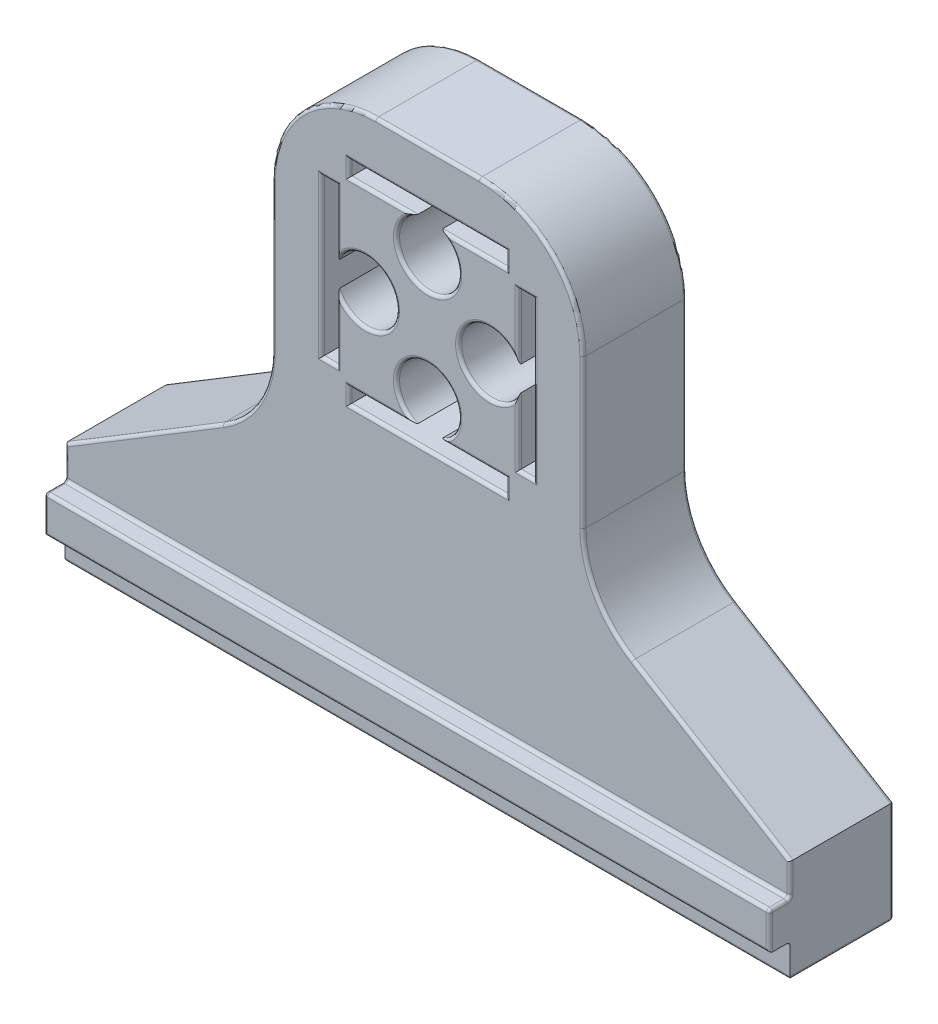
SolidWorks part; units mm, degrees
ref_plane "Front Plane" through (0, 0, 0) normal (0, 0, 1) x (1, 0, 0)
ref_plane "Top Plane" through (0, 0, 0) normal (0, 1, 0) x (1, 0, 0)
ref_plane "Right Plane" through (0, 0, 0) normal (1, 0, 0) x (0, 0, -1)
sketch "Sketch1" plane through (0, 0, 0) normal (0, 0, 1) x (1, 0, 0)
  line L0 (-8.65, 7.69) -> (-8.65, 1.6086)
  line L1 (-8.65, 7.69) -> (-10.35, 7.69)
  line L2 (-10.35, 7.69) -> (-10.35, -7.69)
  line L3 (-10.35, -7.69) -> (-8.65, -7.69)
  line L4 (-6, 0) -> (-10.35, 0) construction
  line L5 (-8.65, -1.6086) -> (-8.65, -7.69)
  line L6 (-8.65, 7.69) -> (-8.65, -7.69) construction
  line L7 (7.69, 8.65) -> (1.6086, 8.65)
  line L8 (7.69, 8.65) -> (7.69, 10.35)
  line L9 (7.69, 10.35) -> (-7.69, 10.35)
  line L10 (-7.69, 10.35) -> (-7.69, 8.65)
  line L11 (8.65, -7.69) -> (8.65, -1.6086)
  line L12 (8.65, -7.69) -> (10.35, -7.69)
  line L13 (10.35, -7.69) -> (10.35, 7.69)
  line L14 (10.35, 7.69) -> (8.65, 7.69)
  line L15 (-7.69, -8.65) -> (-1.6086, -8.65)
  line L16 (-7.69, -8.65) -> (-7.69, -10.35)
  line L17 (-7.69, -10.35) -> (7.69, -10.35)
  line L18 (7.69, -10.35) -> (7.69, -8.65)
  line L19 (1.6086, -8.65) -> (7.69, -8.65)
  line L20 (8.65, 1.6086) -> (8.65, 7.69)
  line L21 (-1.6086, 8.65) -> (-7.69, 8.65)
  circle A0 centre (0, 0) radius 6 construction
  circle A1 centre (0, 6) radius 2
  circle A2 centre (6, 0) radius 2
  circle A3 centre (0, -6) radius 2
  circle A4 centre (-6, 0) radius 2
  arc A5 (-1.6086, 8.65) -> (1.6086, 8.65) centre (0, 6) ccw
  arc A6 (-8.65, -1.6086) -> (-8.65, 1.6086) centre (-6, 0) ccw
  arc A7 (1.6086, -8.65) -> (-1.6086, -8.65) centre (0, -6) ccw
  arc A8 (8.65, 1.6086) -> (8.65, -1.6086) centre (6, 0) ccw
  circle A9 centre (0, 0) radius 2.9 construction
  circle A10 centre (-6, 0) radius 3.1 construction
  circle A11 centre (0, -6) radius 3.1 construction
  circle A12 centre (6, 0) radius 3.1 construction
  circle A13 centre (0, 6) radius 3.1 construction
  point P14 (0, 0)
  point P22 (-10.35, 0)
  point P25 (-5.6596, 0)
  point P43 (0, 0)
  dimension "D1" = 4
  dimension "D4" = 12
  dimension "D5" = 4.35
  dimension "D6" = 1.7
  dimension "D7" = 15.38
  dimension "D3" = 1.1
  dimension "D2" = 4
  dimension "D8" = 4
sketch "Sketch2" plane through (0, 0, 0) normal (0, 0, 1) x (1, 0, 0)
  line L0 (0, 0) -> (0, -37.05) construction
  line L1 (-15, -15) -> (15, -15) construction
  line L2 (-15, -15) -> (-15, 15) construction
  line L3 (-15, 15) -> (15, 15) construction
  line L4 (15, -15) -> (15, 15) construction
  line L5 (-15, -15) -> (15, 15) construction
  line L6 (-15, 15) -> (15, -15) construction
  line L7 (35, -37.05) -> (-35, -37.05) construction
  line L8 (-35, -37.05) -> (-35, -27.15) construction
  line L9 (-35, -27.15) -> (35, -27.15) construction
  line L10 (35, -27.15) -> (35, -37.05) construction
  line L11 (-15, -15) -> (-35, -27.15) construction
  line L12 (15, -15) -> (35, -27.15) construction
  point P0 (0, 0)
  point P11 (0, -37.05)
  dimension "D1" = 30
  dimension "D2" = 37.05
  dimension "D3" = 70
  dimension "D4" = 9.9
sketch "Sketch3" plane through (0, 0, 0) normal (0, 0, 1) x (1, 0, 0)
  line L0 (-7.69, -10.35) -> (7.69, -10.35) construction
  line L1 (7.69, -10.35) -> (7.69, -8.65) construction
  line L2 (1.6086, -8.65) -> (7.69, -8.65) construction
  line L3 (-7.69, -8.65) -> (-1.6086, -8.65) construction
  line L4 (-7.69, -8.65) -> (-7.69, -10.35) construction
  line L5 (10.35, -7.69) -> (10.35, 7.69) construction
  line L6 (10.35, 7.69) -> (8.65, 7.69) construction
  line L7 (8.65, 1.6086) -> (8.65, 7.69) construction
  line L8 (8.65, -7.69) -> (8.65, -1.6086) construction
  line L9 (8.65, -7.69) -> (10.35, -7.69) construction
  line L10 (-1.6086, 8.65) -> (-7.69, 8.65) construction
  line L11 (-7.69, 10.35) -> (-7.69, 8.65) construction
  line L12 (7.69, 10.35) -> (-7.69, 10.35) construction
  line L13 (7.69, 8.65) -> (7.69, 10.35) construction
  line L14 (7.69, 8.65) -> (1.6086, 8.65) construction
  line L15 (-10.35, 7.69) -> (-10.35, -7.69) construction
  line L16 (-10.35, -7.69) -> (-8.65, -7.69) construction
  line L17 (-8.65, -1.6086) -> (-8.65, -7.69) construction
  line L18 (-8.65, 7.69) -> (-8.65, 1.6086) construction
  line L19 (-8.65, 7.69) -> (-10.35, 7.69) construction
  line L20 (-15, -15) -> (-15, 15) construction
  line L21 (-15, 15) -> (15, 15) construction
  line L22 (15, -15) -> (15, 15) construction
  line L23 (15, -15) -> (35, -27.15) construction
  line L24 (-15, -15) -> (-35, -27.15) construction
  line L25 (35, -37.05) -> (-35, -37.05) construction
  line L26 (35, -27.15) -> (35, -37.05) construction
  line L27 (-35, -37.05) -> (-35, -27.15) construction
  line L28 (-7.69, -10.35) -> (7.69, -10.35)
  line L29 (7.69, -10.35) -> (7.69, -8.65)
  line L30 (1.6086, -8.65) -> (7.69, -8.65)
  line L31 (-7.69, -8.65) -> (-1.6086, -8.65)
  line L32 (-7.69, -8.65) -> (-7.69, -10.35)
  line L33 (10.35, -7.69) -> (10.35, 7.69)
  line L34 (10.35, 7.69) -> (8.65, 7.69)
  line L35 (8.65, 1.6086) -> (8.65, 7.69)
  line L36 (8.65, -7.69) -> (8.65, -1.6086)
  line L37 (8.65, -7.69) -> (10.35, -7.69)
  line L38 (-1.6086, 8.65) -> (-7.69, 8.65)
  line L39 (-7.69, 10.35) -> (-7.69, 8.65)
  line L40 (7.69, 10.35) -> (-7.69, 10.35)
  line L41 (7.69, 8.65) -> (7.69, 10.35)
  line L42 (7.69, 8.65) -> (1.6086, 8.65)
  line L43 (-10.35, 7.69) -> (-10.35, -7.69)
  line L44 (-10.35, -7.69) -> (-8.65, -7.69)
  line L45 (-8.65, -1.6086) -> (-8.65, -7.69)
  line L46 (-8.65, 7.69) -> (-8.65, 1.6086)
  line L47 (-8.65, 7.69) -> (-10.35, 7.69)
  line L48 (-15, -15) -> (-15, 15)
  line L49 (-15, 15) -> (15, 15)
  line L50 (15, -15) -> (15, 15)
  line L51 (15, -15) -> (35, -27.15)
  line L52 (-15, -15) -> (-35, -27.15)
  line L53 (35, -37.05) -> (-35, -37.05)
  line L54 (35, -27.15) -> (35, -37.05)
  line L55 (-35, -37.05) -> (-35, -27.15)
  arc A0 (1.6086, -8.65) -> (-1.6086, -8.65) centre (0, -6) ccw construction
  arc A1 (8.65, 1.6086) -> (8.65, -1.6086) centre (6, 0) ccw construction
  arc A2 (-1.6086, 8.65) -> (1.6086, 8.65) centre (0, 6) ccw construction
  arc A3 (-8.65, -1.6086) -> (-8.65, 1.6086) centre (-6, 0) ccw construction
  arc A4 (1.6086, -8.65) -> (-1.6086, -8.65) centre (0, -6) ccw
  arc A5 (8.65, 1.6086) -> (8.65, -1.6086) centre (6, 0) ccw
  arc A6 (-1.6086, 8.65) -> (1.6086, 8.65) centre (0, 6) ccw
  arc A7 (-8.65, -1.6086) -> (-8.65, 1.6086) centre (-6, 0) ccw
  circle A8 centre (0, -6) radius 2 construction
  circle A9 centre (6, 0) radius 2 construction
  circle A10 centre (0, 6) radius 2 construction
  circle A11 centre (-6, 0) radius 2 construction
  circle A12 centre (0, -6) radius 2
  circle A13 centre (6, 0) radius 2
  circle A14 centre (0, 6) radius 2
  circle A15 centre (-6, 0) radius 2
extrude "Boss-Extrude1" add sketch "Sketch3" along normal mid plane 10 contours L55 L53 L54 L51 L50 L49 L48 L52 A7 L45 L44 L43 L47 L46 A6 L38 L39 L40 L41 L42 A5 L35 L34 L33 L37 L36 A4 L30 L29 L28 L32 L31
sketch "Sketch4" plane through (0, 0, -5) normal (0, 0, -1) x (-1, 0, 0)
  line L0 (7.69, -8.65) -> (1.6086, -8.65) construction
  line L1 (7.69, -8.65) -> (7.69, -10.35) construction
  line L2 (7.69, -10.35) -> (-7.69, -10.35) construction
  line L3 (-7.69, -10.35) -> (-7.69, -8.65) construction
  line L4 (-1.6086, -8.65) -> (-7.69, -8.65) construction
  line L5 (8.65, 7.69) -> (8.65, 1.6086) construction
  line L6 (8.65, 7.69) -> (10.35, 7.69) construction
  line L7 (10.35, 7.69) -> (10.35, -7.69) construction
  line L8 (10.35, -7.69) -> (8.65, -7.69) construction
  line L9 (8.65, -1.6086) -> (8.65, -7.69) construction
  line L10 (1.6086, 8.65) -> (7.69, 8.65) construction
  line L11 (7.69, 10.35) -> (7.69, 8.65) construction
  line L12 (-7.69, 10.35) -> (7.69, 10.35) construction
  line L13 (-7.69, 8.65) -> (-7.69, 10.35) construction
  line L14 (-7.69, 8.65) -> (-1.6086, 8.65) construction
  line L15 (-8.65, 1.6086) -> (-8.65, 7.69) construction
  line L16 (-10.35, 7.69) -> (-8.65, 7.69) construction
  line L17 (-10.35, -7.69) -> (-10.35, 7.69) construction
  line L18 (-8.65, -7.69) -> (-10.35, -7.69) construction
  line L19 (-8.65, -7.69) -> (-8.65, -1.6086) construction
  line L20 (7.69, -8.65) -> (1.6086, -8.65)
  line L21 (7.69, -8.65) -> (7.69, -10.35)
  line L22 (7.69, -10.35) -> (-7.69, -10.35)
  line L23 (-7.69, -10.35) -> (-7.69, -8.65)
  line L24 (-1.6086, -8.65) -> (-7.69, -8.65)
  line L25 (8.65, 7.69) -> (8.65, 1.6086)
  line L26 (8.65, 7.69) -> (10.35, 7.69)
  line L27 (10.35, 7.69) -> (10.35, -7.69)
  line L28 (10.35, -7.69) -> (8.65, -7.69)
  line L29 (8.65, -1.6086) -> (8.65, -7.69)
  line L30 (1.6086, 8.65) -> (7.69, 8.65)
  line L31 (7.69, 10.35) -> (7.69, 8.65)
  line L32 (-7.69, 10.35) -> (7.69, 10.35)
  line L33 (-7.69, 8.65) -> (-7.69, 10.35)
  line L34 (-7.69, 8.65) -> (-1.6086, 8.65)
  line L35 (-8.65, 1.6086) -> (-8.65, 7.69)
  line L36 (-10.35, 7.69) -> (-8.65, 7.69)
  line L37 (-10.35, -7.69) -> (-10.35, 7.69)
  line L38 (-8.65, -7.69) -> (-10.35, -7.69)
  line L39 (-8.65, -7.69) -> (-8.65, -1.6086)
  circle A0 centre (6, 0) radius 2 construction
  circle A1 centre (0, 6) radius 2 construction
  circle A2 centre (-6, 0) radius 2 construction
  circle A3 centre (0, -6) radius 2 construction
  arc A4 (1.6086, -8.65) -> (-1.6086, -8.65) centre (0, -6) ccw construction
  arc A5 (8.65, 1.6086) -> (8.65, -1.6086) centre (6, 0) ccw construction
  arc A6 (-1.6086, 8.65) -> (1.6086, 8.65) centre (0, 6) ccw construction
  arc A7 (-8.65, -1.6086) -> (-8.65, 1.6086) centre (-6, 0) ccw construction
  circle A8 centre (6, 0) radius 2
  circle A9 centre (0, 6) radius 2
  circle A10 centre (-6, 0) radius 2
  circle A11 centre (0, -6) radius 2
  arc A12 (1.6086, -8.65) -> (-1.6086, -8.65) centre (0, -6) ccw
  arc A13 (8.65, 1.6086) -> (8.65, -1.6086) centre (6, 0) ccw
  arc A14 (-1.6086, 8.65) -> (1.6086, 8.65) centre (0, 6) ccw
  arc A15 (-8.65, -1.6086) -> (-8.65, 1.6086) centre (-6, 0) ccw
extrude "Boss-Extrude2" add sketch "Sketch4" against normal blind 2
fillet "Fillet1" radius 10 4 edges at (15, -15, 0) (15, 15, 0) (-15, 15, 0) (-15, -15, 0)
sketch "Sketch5" plane through (35, 0, 0) normal (1, 0, 0) x (0, 0, -1)
  line L0 (-7, -33.85) -> (-5, -33.85)
  line L1 (-5, -33.85) -> (-5, -37.05)
  line L2 (-5, -37.05) -> (4.9, -37.05)
  line L3 (4.9, -37.05) -> (4.9, -27.15)
  line L4 (4.9, -27.15) -> (-5, -27.15)
  line L5 (-5, -27.15) -> (-5, -30.25)
  line L6 (-5, -30.25) -> (-7, -30.25)
  line L7 (-7, -30.25) -> (-7, -33.85)
  point P0 (-5, -37.05)
extrude "Boss-Extrude3" add sketch "Sketch5" against normal up to surface (70 mm away) up to face at (-35, -32.1, 0)
fillet "Fillet2" radius 0.3 6 edges at (35, -32.05, 7) (0, -33.85, 7) (-35, -32.05, 7) (0, -30.25, 7) (0, -33.85, 5) (0, -30.25, 5)
sketch "Sketch6" plane through (0, 0, -3) normal (0, 0, 1) x (1, 0, 0)
  line L15 (-8.75, -7.59) -> (-8.75, -1.199)
  line L16 (-10.25, -7.59) -> (-8.75, -7.59)
  line L17 (-10.25, 7.59) -> (-10.25, -7.59)
  line L18 (-8.75, 7.59) -> (-10.25, 7.59)
  line L19 (-8.75, 1.199) -> (-8.75, 7.59)
  line L20 (-8.75, -7.59) -> (-8.75, -1.199)
  line L21 (-10.25, -7.59) -> (-8.75, -7.59)
  line L22 (-10.25, 7.59) -> (-10.25, -7.59)
  line L23 (-8.75, 7.59) -> (-10.25, 7.59)
  line L24 (-8.75, 1.199) -> (-8.75, 7.59)
  line L30 (-7.59, 8.75) -> (-1.199, 8.75)
  line L31 (-7.59, 10.25) -> (-7.59, 8.75)
  line L32 (7.59, 10.25) -> (-7.59, 10.25)
  line L33 (7.59, 8.75) -> (7.59, 10.25)
  line L34 (1.199, 8.75) -> (7.59, 8.75)
  line L35 (-7.59, 8.75) -> (-1.199, 8.75)
  line L36 (-7.59, 10.25) -> (-7.59, 8.75)
  line L37 (7.59, 10.25) -> (-7.59, 10.25)
  line L38 (7.59, 8.75) -> (7.59, 10.25)
  line L39 (1.199, 8.75) -> (7.59, 8.75)
  line L45 (8.75, 7.59) -> (8.75, 1.199)
  line L46 (10.25, 7.59) -> (8.75, 7.59)
  line L47 (10.25, -7.59) -> (10.25, 7.59)
  line L48 (8.75, -7.59) -> (10.25, -7.59)
  line L49 (8.75, -1.199) -> (8.75, -7.59)
  line L50 (8.75, 7.59) -> (8.75, 1.199)
  line L51 (10.25, 7.59) -> (8.75, 7.59)
  line L52 (10.25, -7.59) -> (10.25, 7.59)
  line L53 (8.75, -7.59) -> (10.25, -7.59)
  line L54 (8.75, -1.199) -> (8.75, -7.59)
  line L56 (1.6086, -8.65) -> (7.69, -8.65) construction
  line L57 (7.69, -10.35) -> (7.69, -8.65) construction
  line L58 (-7.69, -10.35) -> (7.69, -10.35) construction
  line L59 (-7.69, -8.65) -> (-7.69, -10.35) construction
  line L60 (7.59, -8.75) -> (1.199, -8.75)
  line L61 (7.59, -10.25) -> (7.59, -8.75)
  line L62 (-7.59, -10.25) -> (7.59, -10.25)
  line L63 (-7.59, -8.75) -> (-7.59, -10.25)
  line L64 (-1.199, -8.75) -> (-7.59, -8.75)
  line L65 (7.59, -8.75) -> (1.199, -8.75)
  line L66 (7.59, -10.25) -> (7.59, -8.75)
  line L67 (-7.59, -10.25) -> (7.59, -10.25)
  line L68 (-7.59, -8.75) -> (-7.59, -10.25)
  line L69 (-1.199, -8.75) -> (-7.59, -8.75)
  line L70 (-7.69, -8.65) -> (-1.6086, -8.65) construction
  line L71 (10.35, 7.69) -> (8.65, 7.69) construction
  line L72 (8.65, 1.6086) -> (8.65, 7.69) construction
  line L73 (8.65, -7.69) -> (8.65, -1.6086) construction
  line L74 (8.65, -7.69) -> (10.35, -7.69) construction
  line L75 (10.35, -7.69) -> (10.35, 7.69) construction
  line L76 (7.69, 10.35) -> (-7.69, 10.35) construction
  line L77 (-7.69, 10.35) -> (-7.69, 8.65) construction
  line L78 (-1.6086, 8.65) -> (-7.69, 8.65) construction
  line L79 (7.69, 8.65) -> (1.6086, 8.65) construction
  line L80 (7.69, 8.65) -> (7.69, 10.35) construction
  line L81 (-8.65, 7.69) -> (-10.35, 7.69) construction
  line L82 (-10.35, 7.69) -> (-10.35, -7.69) construction
  line L83 (-10.35, -7.69) -> (-8.65, -7.69) construction
  line L84 (-8.65, -1.6086) -> (-8.65, -7.69) construction
  line L85 (-8.65, 7.69) -> (-8.65, 1.6086) construction
  line L86 (1.6086, -8.65) -> (7.69, -8.65)
  line L87 (7.69, -10.35) -> (7.69, -8.65)
  line L88 (-7.69, -10.35) -> (7.69, -10.35)
  line L89 (-7.69, -8.65) -> (-7.69, -10.35)
  line L90 (-7.69, -8.65) -> (-1.6086, -8.65)
  line L91 (10.35, 7.69) -> (8.65, 7.69)
  line L92 (8.65, 1.6086) -> (8.65, 7.69)
  line L93 (8.65, -7.69) -> (8.65, -1.6086)
  line L94 (8.65, -7.69) -> (10.35, -7.69)
  line L95 (10.35, -7.69) -> (10.35, 7.69)
  line L96 (7.69, 10.35) -> (-7.69, 10.35)
  line L97 (-7.69, 10.35) -> (-7.69, 8.65)
  line L98 (-1.6086, 8.65) -> (-7.69, 8.65)
  line L99 (7.69, 8.65) -> (1.6086, 8.65)
  line L100 (7.69, 8.65) -> (7.69, 10.35)
  line L101 (-8.65, 7.69) -> (-10.35, 7.69)
  line L102 (-10.35, 7.69) -> (-10.35, -7.69)
  line L103 (-10.35, -7.69) -> (-8.65, -7.69)
  line L104 (-8.65, -1.6086) -> (-8.65, -7.69)
  line L105 (-8.65, 7.69) -> (-8.65, 1.6086)
  arc A10 (-8.75, -1.199) -> (-8.75, 1.199) centre (-6, 0) ccw
  arc A11 (-8.75, -1.199) -> (-8.75, 1.199) centre (-6, 0) ccw
  arc A13 (-1.199, 8.75) -> (1.199, 8.75) centre (0, 6) ccw
  arc A14 (-1.199, 8.75) -> (1.199, 8.75) centre (0, 6) ccw
  arc A16 (8.75, 1.199) -> (8.75, -1.199) centre (6, 0) ccw
  arc A17 (8.75, 1.199) -> (8.75, -1.199) centre (6, 0) ccw
  arc A18 (1.6086, -8.65) -> (-1.6086, -8.65) centre (0, -6) ccw construction
  arc A19 (1.199, -8.75) -> (-1.199, -8.75) centre (0, -6) ccw
  arc A20 (1.199, -8.75) -> (-1.199, -8.75) centre (0, -6) ccw
  arc A21 (8.65, 1.6086) -> (8.65, -1.6086) centre (6, 0) ccw construction
  arc A22 (-1.6086, 8.65) -> (1.6086, 8.65) centre (0, 6) ccw construction
  arc A23 (-8.65, -1.6086) -> (-8.65, 1.6086) centre (-6, 0) ccw construction
  arc A24 (1.6086, -8.65) -> (-1.6086, -8.65) centre (0, -6) ccw
  arc A25 (8.65, 1.6086) -> (8.65, -1.6086) centre (6, 0) ccw
  arc A26 (-1.6086, 8.65) -> (1.6086, 8.65) centre (0, 6) ccw
  arc A27 (-8.65, -1.6086) -> (-8.65, 1.6086) centre (-6, 0) ccw
  dimension "D1" = 0.1
  dimension "D2" = 0.1
  dimension "D3" = 0.1
  dimension "D4" = 0.1
extrude "Boss-Extrude4" add sketch "Sketch6" along normal up to surface (8 mm away) up to face at (0, -10.4923, 5)
fillet "Fillet3" radius 0.3 4 edges at (-35, -37.05, 0) (0, -37.05, 5) (35, -37.05, 0) (0, -37.05, -5)
fillet "Fillet4" radius 0.3 17 edges at (-34.9121, -36.9621, -4.9121) (34.9121, -36.9621, -4.9121) (4, 0, -5) (-2, 6, -5) (-8, 0, -5) (-2, -6, -5) (27.404, -22.5354, -5) (16.2845, -14.2774, -5) (15, -2.1872, -5) (12.0711, 12.0711, -5) (0, 15, -5) (-12.0711, 12.0711, -5) (-15, -2.1872, -5) (-16.2845, -14.2774, -5) (-27.404, -22.5354, -5) (-35, -31.95, -5) (35, -31.95, -5)
fillet "Fillet5" radius 0.3 41 edges at (35, -28.55, 5) (15, -2.1872, 5) (27.404, -22.5354, 5) (0, 15, 5) (-15, -2.1872, 5) (-27.404, -22.5354, 5) (-12.0711, 12.0711, 5) (12.0711, 12.0711, 5) (16.2845, -14.2774, 5) (-16.2845, -14.2774, 5) (35, -30.25, 6) (-35, -30.25, 6) (-35, -28.55, 5) (35, -30.1621, 5.0879) (-35, -30.1621, 5.0879) (-34.9121, -30.3379, 6.9121) (34.9121, -30.3379, 6.9121) (0, -10.25, 5) (-7.59, -9.5, 5) (-4.3945, -8.75, 5) (0, -3, 5) (4.3945, -8.75, 5) (7.59, -9.5, 5) (10.25, 0, 5) (9.5, -7.59, 5) (8.75, -4.3945, 5) (3, 0, 5) (8.75, 4.3945, 5) (9.5, 7.59, 5) (0, 10.25, 5) (7.59, 9.5, 5) (4.3945, 8.75, 5) (0, 3, 5) (-4.3945, 8.75, 5) (-7.59, 9.5, 5) (-10.25, 0, 5) (-9.5, 7.59, 5) (-8.75, 4.3945, 5) (-3, 0, 5) (-8.75, -4.3945, 5) (-9.5, -7.59, 5)
